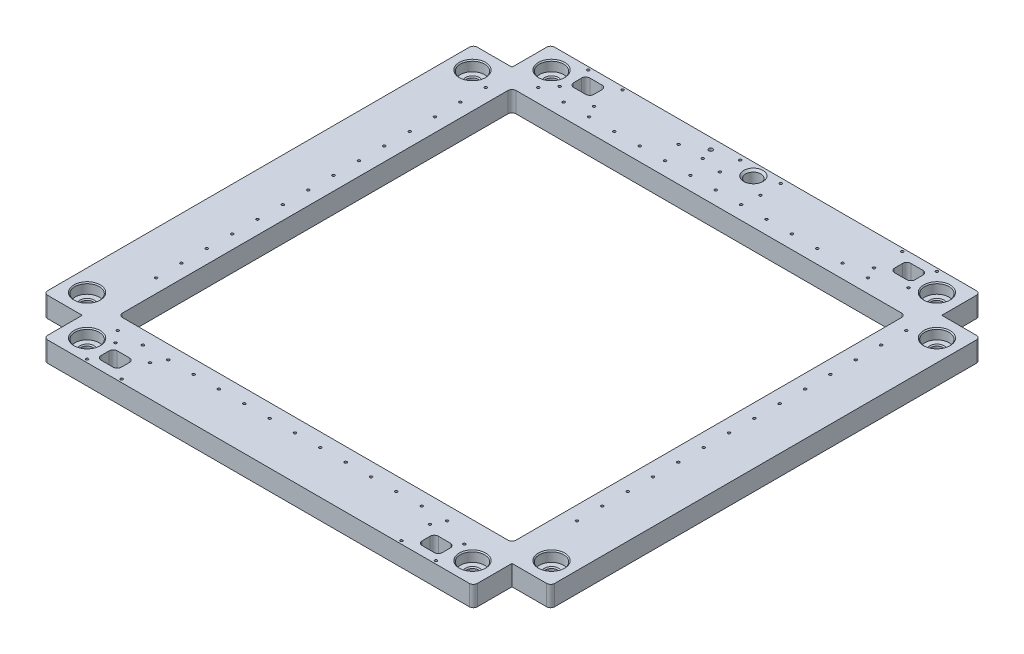
SolidWorks part; units mm, degrees
material "ASTM A36 Steel"
ref_plane "Front Plane" through (0, 0, 0) normal (0, 0, 1) x (1, 0, 0)
ref_plane "Top Plane" through (0, 0, 0) normal (0, 1, 0) x (1, 0, 0)
ref_plane "Right Plane" through (0, 0, 0) normal (1, 0, 0) x (0, 0, -1)
sketch "Sketch1" plane through (0, 0, 0) normal (0, 1, 0) x (1, 0, 0)
  line L1 (250, -250) -> (-250, -250)
  line L2 (250, -250) -> (250, 250)
  line L3 (250, 250) -> (-250, 250)
  line L4 (-250, -250) -> (-250, 250)
  line L5 (250, -250) -> (-250, 250) construction
  line L6 (250, 250) -> (-250, -250) construction
  point P0 (0, 0)
  dimension "D1" = 500
  dimension "D2" = 500
extrude "Boss-Extrude1" add sketch "Sketch1" along normal blind 20
sketch "Sketch2" plane through (0, 20, 0) normal (0, 1, 0) x (1, 0, 0)
  line L0 (250, 250) -> (-250, 250) construction
  line L10 (-250, 250) -> (-250, -250) construction
  line L15 (-250, 169) -> (-208, 169)
  line L16 (-250, 169) -> (-250, 211)
  line L17 (-174.5, 213.5) -> (-205.5, 213.5)
  line L27 (-250, 211) -> (-208, 211)
  line L33 (-208, 169) -> (-208, 211)
  line L35 (-250, 169) -> (-208, 211) construction
  line L36 (-250, 211) -> (-208, 169) construction
  line L37 (-169, 208) -> (-211, 208)
  line L38 (-169, 208) -> (-169, 250)
  line L39 (-169, 250) -> (-211, 250)
  line L40 (-211, 208) -> (-211, 250)
  line L41 (-169, 208) -> (-211, 250) construction
  line L42 (-169, 250) -> (-211, 208) construction
  line L43 (-208, 206) -> (-213, 211)
  line L44 (-174.5, 213.5) -> (-174.5, 244.5)
  line L45 (-174.5, 244.5) -> (-205.5, 244.5)
  line L46 (-205.5, 213.5) -> (-205.5, 244.5)
  line L47 (-174.5, 213.5) -> (-205.5, 244.5) construction
  line L48 (-174.5, 244.5) -> (-205.5, 213.5) construction
  line L49 (-213.5, 174.5) -> (-244.5, 174.5)
  line L50 (-213.5, 174.5) -> (-213.5, 205.5)
  line L51 (-213.5, 205.5) -> (-244.5, 205.5)
  line L52 (-244.5, 174.5) -> (-244.5, 205.5)
  line L53 (-213.5, 174.5) -> (-244.5, 205.5) construction
  line L54 (-213.5, 205.5) -> (-244.5, 174.5) construction
  line L55 (-206, 208) -> (-211, 213)
  line L56 (-213, 211) -> (-211, 213) construction
  point P1 (-229, 190)
  point P5 (-190, 229)
  point P23 (-229, 190)
  point P27 (-190, 229)
  dimension "D1" = 5
  dimension "D2" = 45
  dimension "D3" = 42
  dimension "D4" = 31
  dimension "D5" = 45
  dimension "D6" = 5
  dimension "D7" = 60
hole_wizard "Bearing Press Fit" positions "Sketch8" profile "Sketch9" hole size "Ø12.0" standard "ANSI Metric" end condition through all
sketch "Sketch8" plane through (0, 20, 0) normal (0, 1, 0) x (1, 0, 0)
  line L1 (-169, 250) -> (-211, 208) construction
  point P8 (-190, 229)
  point P12 (-229, 190)
sketch "Sketch9" plane through (-190, 20, -229) normal (1, 0, 0) x (0, 0, 1)
  line L0 (0, 0) -> (0, 20)
  line L1 (0, 20) -> (6, 20)
  line L2 (6, 20) -> (6, 0)
  line L5 (6, 0) -> (0, 0)
  line L11 (0, -6.35) -> (0, 107.95) construction
  dimension "Thru Hole Dia." = 12
  dimension "Thru Hole Depth" = 20
ref_axis "Axis1" through (0, 21, 0) along (0, -1, 0)
pattern_circular "CirPattern1" count 4 over 360 about axis through (0, 21, 0) along (0, -1, 0) of "Bearing Press Fit"
sketch "Sketch5" plane through (0, 20, 0) normal (0, 1, 0) x (1, 0, 0)
  line L1 (194, -194) -> (-194, -194)
  line L2 (194, -194) -> (194, 194)
  line L3 (194, 194) -> (-194, 194)
  line L4 (-194, -194) -> (-194, 194)
  line L5 (194, -194) -> (-194, 194) construction
  line L6 (194, 194) -> (-194, -194) construction
  point P0 (0, 0)
  dimension "D1" = 388
extrude "Cut-Extrude1" cut sketch "Sketch5" against normal up to surface (20 mm away) up to face at (-229, 0, 196)
sketch "Sketch10" plane through (0, 0, 0) normal (0, 1, 0) x (1, 0, 0)
  line L5 (194, 194) -> (-194, 194) construction
  line L6 (214, -214) -> (-214, -214)
  line L14 (214, -214) -> (214, 214)
  line L15 (214, 214) -> (-214, 214)
  line L16 (-214, -214) -> (-214, 214)
  line L17 (214, -214) -> (-214, 214) construction
  line L18 (214, 214) -> (-214, -214) construction
  line L19 (201.5, -201.5) -> (-201.5, -201.5)
  line L20 (201.5, -201.5) -> (201.5, 201.5)
  line L21 (201.5, 201.5) -> (-201.5, 201.5)
  line L22 (-201.5, -201.5) -> (-201.5, 201.5)
  line L23 (201.5, -201.5) -> (-201.5, 201.5) construction
  line L24 (201.5, 201.5) -> (-201.5, -201.5) construction
  point P0 (0, 0)
  point P6 (0, 0)
  dimension "D2" = 7.5
  dimension "D1" = 12.5
extrude "Linear Rail Slot" cut sketch "Sketch10" along normal blind 2.5
fillet "Fillet2" radius 4 4 edges at (-194, 10, 194) (194, 10, 194) (194, 10, -194) (-194, 10, -194)
sketch "Sketch11" plane through (0, 2.5, 0) normal (0, -1, 0) x (1, 0, 0)
  line L0 (-204, 207.5) -> (156, 207.5)
  line L1 (-201.5, 201.5) -> (201.5, 201.5) construction
  line L3 (-214, -214) -> (-214, 214) construction
  point P16 (143.5, 207.5)
  point P18 (118.5, 207.5)
  point P19 (93.5, 207.5)
  point P20 (68.5, 207.5)
  point P21 (43.5, 207.5)
  point P22 (18.5, 207.5)
  point P23 (-6.5, 207.5)
  point P24 (-31.5, 207.5)
  point P25 (-56.5, 207.5)
  point P26 (-81.5, 207.5)
  point P28 (-106.5, 207.5)
  point P29 (-131.5, 207.5)
  point P30 (-156.5, 207.5)
  point P31 (-181.5, 207.5)
  dimension "D1" = 360
  dimension "D2" = 6
  dimension "D4" = 14
  dimension "D5" = 25
  dimension "D6" = 10
  dimension "D3" = 12.5
hole_wizard "Tap Drill for M3x0.5 Tap1" positions "Sketch12" profile "Sketch13" hole size "M3x0.5" standard "ANSI Metric" end condition through all
sketch "Sketch12" plane through (0, 2.5, 0) normal (0, -1, 0) x (-1, 0, 0)
  line L0 (204, -207.5) -> (-156, -207.5) construction
  point P28 (-143.5, -207.5)
  point P31 (-118.5, -207.5)
  point P34 (-93.5, -207.5)
  point P37 (-68.5, -207.5)
  point P40 (-43.5, -207.5)
  point P43 (-18.5, -207.5)
  point P46 (6.5, -207.5)
  point P49 (31.5, -207.5)
  point P51 (56.5, -207.5)
  point P54 (81.5, -207.5)
  point P57 (106.5, -207.5)
  point P61 (131.5, -207.5)
  point P64 (156.5, -207.5)
  point P67 (181.5, -207.5)
sketch "Sketch13" plane through (143.5, 2.5, 207.5) normal (1, 0, 0) x (0, 0, -1)
  line L0 (0, 0) -> (0, 17.5)
  line L1 (0, 17.5) -> (1.25, 17.5)
  line L2 (1.25, 17.5) -> (1.25, 0)
  line L5 (1.25, 0) -> (0, 0)
  line L11 (0, -6.35) -> (0, 107.95) construction
  dimension "Thru Hole Dia." = 2.5
  dimension "Thru Hole Depth" = 17.5
sketch "Sketch14" plane through (0, 0, 0) normal (0, -1, 0) x (1, 0, 0)
  line L1 (-156.5, 213.5) -> (-181.5, 213.5)
  line L2 (-152.5, 217.5) -> (-152.5, 219.5)
  line L3 (-156.5, 223.5) -> (-181.5, 223.5)
  line L4 (-185.5, 217.5) -> (-185.5, 219.5)
  line L5 (-152.5, 213.5) -> (-185.5, 223.5) construction
  line L6 (-152.5, 223.5) -> (-185.5, 213.5) construction
  line L7 (-201.5, 201.5) -> (201.5, 201.5) construction
  line L8 (-181.5, 207.5) -> (-156.5, 207.5) construction
  line L19 (-6.5, 213.5) -> (-31.5, 213.5)
  line L25 (-2.5, 217.5) -> (-2.5, 219.5)
  line L26 (-6.5, 223.5) -> (-31.5, 223.5)
  line L31 (-35.5, 217.5) -> (-35.5, 219.5)
  line L32 (-2.5, 213.5) -> (-35.5, 223.5) construction
  line L33 (-2.5, 223.5) -> (-35.5, 213.5) construction
  line L34 (-31.5, 207.5) -> (-6.5, 207.5) construction
  line L35 (143.5, 213.5) -> (118.5, 213.5)
  line L36 (147.5, 217.5) -> (147.5, 219.5)
  line L37 (143.5, 223.5) -> (118.5, 223.5)
  line L38 (114.5, 217.5) -> (114.5, 219.5)
  line L39 (147.5, 213.5) -> (114.5, 223.5) construction
  line L40 (147.5, 223.5) -> (114.5, 213.5) construction
  line L41 (118.5, 207.5) -> (143.5, 207.5) construction
  arc A3 (-152.5, 219.5) -> (-156.5, 223.5) centre (-156.5, 219.5) ccw
  arc A4 (-156.5, 213.5) -> (-152.5, 217.5) centre (-156.5, 217.5) ccw
  arc A5 (-181.5, 213.5) -> (-185.5, 217.5) centre (-181.5, 217.5) cw
  arc A6 (-181.5, 223.5) -> (-185.5, 219.5) centre (-181.5, 219.5) ccw
  arc A7 (-2.5, 219.5) -> (-6.5, 223.5) centre (-6.5, 219.5) ccw
  arc A8 (-6.5, 213.5) -> (-2.5, 217.5) centre (-6.5, 217.5) ccw
  arc A9 (-31.5, 213.5) -> (-35.5, 217.5) centre (-31.5, 217.5) cw
  arc A10 (-31.5, 223.5) -> (-35.5, 219.5) centre (-31.5, 219.5) ccw
  arc A11 (147.5, 219.5) -> (143.5, 223.5) centre (143.5, 219.5) ccw
  arc A12 (143.5, 213.5) -> (147.5, 217.5) centre (143.5, 217.5) ccw
  arc A13 (118.5, 213.5) -> (114.5, 217.5) centre (118.5, 217.5) cw
  arc A14 (118.5, 223.5) -> (114.5, 219.5) centre (118.5, 219.5) ccw
  point P0 (-169, 218.5)
  point P12 (-169, 207.5)
  point P26 (-19, 218.5)
  point P45 (131, 218.5)
  dimension "D5" = 3
  dimension "D4" = 4
  dimension "D1" = 33
  dimension "D2" = 12
  dimension "D3" = 10
  dimension "D7" = 25
  dimension "D6" = 150
mirror "Mirror5" about plane through (0, 0, 0) normal (0, 0, 1) of "Tap Drill for M3x0.5 Tap1"
ref_plane "Plane1" through (0, 0, 0) normal (-0.7071, 0, 0.7071) x (0.7071, 0, 0.7071)
mirror "Mirror6" about plane through (0, 0, 0) normal (-0.7071, 0, 0.7071) of "Mirror5"
sketch "Sketch19" plane through (0, 2.5, 0) normal (0, -1, 0) x (1, 0, 0)
  line L0 (-198.5, 201.5) -> (-198.5, 214)
  line L1 (-201.5, 201.5) -> (201.5, 201.5) construction
  line L2 (-214, 214) -> (214, 214) construction
  line L3 (-198.5, 214) -> (-214, 214)
  line L4 (-214, 214) -> (-214, 198.5)
  line L5 (-214, -214) -> (-214, 214) construction
  line L6 (-214, 198.5) -> (-201.5, 198.5)
  line L7 (-201.5, -201.5) -> (-201.5, 201.5) construction
  line L8 (-201.5, 198.5) -> (-201.5, 201.5)
  line L9 (-201.5, 201.5) -> (-198.5, 201.5)
  dimension "D1" = 3
extrude "Boss-Extrude2" add sketch "Sketch19" along normal up to surface (2.5 mm away) up to face at (-229, 0, 196)
pattern_circular "CirPattern4" count 4 over 360 about axis through (0, 21, 0) along (0, -1, 0) of "Boss-Extrude2"
sketch "Sketch20" plane through (0, 20, 0) normal (0, 1, 0) x (1, 0, 0)
  line L5 (-250, -250) -> (250, -250) construction
  line L20 (148.3, -225) -> (168.3, -241) construction
  line L23 (168.3, -225) -> (148.3, -241) construction
  line L28 (122, -247) -> (172, -219) construction
  line L29 (172, -247) -> (122, -219) construction
  line L30 (172, -219) -> (122, -219) construction
  line L31 (122, -247) -> (122, -219) construction
  line L32 (172, -247) -> (122, -247) construction
  line L33 (172, -247) -> (172, -219) construction
  line L34 (164.3, -241) -> (152.3, -241)
  line L35 (148.3, -229) -> (148.3, -237)
  line L36 (164.3, -225) -> (152.3, -225)
  line L37 (168.3, -229) -> (168.3, -237)
  arc A12 (152.3, -225) -> (148.3, -229) centre (152.3, -229) ccw
  arc A13 (148.3, -237) -> (152.3, -241) centre (152.3, -237) ccw
  arc A14 (168.3, -237) -> (164.3, -241) centre (164.3, -237) cw
  arc A15 (168.3, -229) -> (164.3, -225) centre (164.3, -229) ccw
  circle A16 centre (190, -229) radius 6 construction
  point P8 (0, 0)
  point P65 (158.3, -233)
  point P66 (147, -233)
  point P67 (158.3, -233)
  dimension "D7" = 31.7
  dimension "D8" = 11.3
  dimension "D6" = 4
  dimension "D1" = 28
  dimension "D2" = 50
  dimension "D3" = 17
  dimension "D4" = 20
  dimension "D5" = 16
extrude "Cut-Extrude3" cut sketch "Sketch20" against normal through all
hole_wizard "Tap Drill for M3x0.5 Tap6" positions "Sketch39" profile "Sketch40" hole size "M3x0.5" standard "ANSI Metric"
sketch "Sketch39" plane through (0, 20, 0) normal (0, 1, 0) x (1, 0, 0)
  line L1 (172, -247) -> (138, -247)
  line L2 (172, -247) -> (172, -219)
  line L3 (172, -219) -> (138, -219)
  line L4 (138, -247) -> (138, -219)
  line L5 (-250, -250) -> (250, -250) construction
  circle A0 centre (190, -229) radius 6 construction
  point P1 (172, -247)
  point P2 (138, -219)
  point P99 (172, -219)
  point P100 (138, -247)
  dimension "D1" = 34
  dimension "D2" = 28
  dimension "D3" = 3
  dimension "D4" = 18
sketch "Sketch40" plane through (172, 20, 247) normal (1, 0, 0) x (0, 0, 1)
  line L0 (0, 0) -> (0, 20)
  line L1 (0, 20) -> (1.25, 20)
  line L2 (1.25, 20) -> (1.25, 0)
  line L5 (1.25, 0) -> (0, 0)
  line L10 (0, 20) -> (-1.25, 20) construction
  line L11 (0, -6.35) -> (0, 107.95) construction
  dimension "Hole Dia." = 2.5
  dimension "Hole Depth" = 20
  dimension "Drill Angle" = 180
mirror "Mirror8" about plane through (0, 0, 0) normal (1, 0, 0) of "Tap Drill for M3x0.5 Tap6", "Cut-Extrude3"
mirror "Mirror9" about plane through (0, 0, 0) normal (0, 0, 1) of "Mirror8"
sketch "Sketch27" plane through (0, 20, 0) normal (0, 1, 0) x (1, 0, 0)
  line L1 (250, -250) -> (211.9, -250)
  line L2 (250, -250) -> (250, -211.9)
  line L3 (250, -211.9) -> (211.9, -211.9)
  line L4 (211.9, -250) -> (211.9, -211.9)
  dimension "D1" = 38.1
extrude "Cut-Extrude4" cut sketch "Sketch27" against normal up to surface (20 mm away) up to face at (172, 0, -245.75)
pattern_circular "CirPattern3" count 4 over 360 about axis through (0, 21, 0) along (0, -1, 0) of "Cut-Extrude4"
fillet "Fillet5" radius 4 16 edges at (198.5, 1.25, 214) (198.5, 1.25, 201.5) (201.5, 1.25, 198.5) (214, 1.25, 198.5) (-214, 1.25, 198.5) (-198.5, 1.25, 214) (-201.5, 1.25, 198.5) (-198.5, 1.25, 201.5) (-214, 1.25, -198.5) (-198.5, 1.25, -214) (-198.5, 1.25, -201.5) (-201.5, 1.25, -198.5) (198.5, 1.25, -201.5) (198.5, 1.25, -214) (201.5, 1.25, -198.5) (214, 1.25, -198.5)
hole_wizard "Tap Drill for M3x0.5 Tap4" positions "Sketch35" profile "Sketch36" hole size "M3x0.5" standard "ANSI Metric" end condition up to next
sketch "Sketch35" plane through (0, 20, 0) normal (0, 1, 0) x (1, 0, 0)
  line L1 (20, 225) -> (-20, 225)
  line L2 (20, 225) -> (20, 245)
  line L3 (20, 245) -> (-20, 245)
  line L4 (-20, 225) -> (-20, 245)
  line L5 (20, 225) -> (-20, 245) construction
  line L6 (20, 245) -> (-20, 225) construction
  line L7 (211.9, 250) -> (-211.9, 250) construction
  point P2 (-20, 245)
  point P53 (20, 225)
  point P54 (20, 245)
  point P55 (-20, 225)
  point P69 (0, 235)
  dimension "D1" = 20
  dimension "D2" = 40
  dimension "D3" = 15
sketch "Sketch36" plane through (-20, 20, -245) normal (1, 0, 0) x (0, 0, 1)
  line L0 (0, 0) -> (0, 20)
  line L1 (0, 20) -> (1.25, 20)
  line L2 (1.25, 20) -> (1.25, 0)
  line L5 (1.25, 0) -> (0, 0)
  line L11 (0, -6.35) -> (0, 107.95) construction
  dimension "Thru Hole Dia." = 2.5
  dimension "Thru Hole Depth" = 20
hole_wizard "Ø15.0 (15) Diameter Hole2" positions "Sketch37" profile "Sketch38" hole size "Ø15.0" standard "ANSI Metric" end condition up to next
sketch "Sketch37" plane through (0, 20, 0) normal (0, 1, 0) x (1, 0, 0)
  circle A0 centre (0, 235) radius 1.25 construction
  point P0 (0, 238)
  dimension "D1" = 3
sketch "Sketch38" plane through (0, 20, -238) normal (1, 0, 0) x (0, 0, 1)
  line L0 (0, 0) -> (0, 20)
  line L1 (0, 20) -> (7.5, 20)
  line L2 (7.5, 20) -> (7.5, 0)
  line L5 (7.5, 0) -> (0, 0)
  line L11 (0, -6.35) -> (0, 107.95) construction
  dimension "Thru Hole Dia." = 15
  dimension "Thru Hole Depth" = 20
chamfer "Chamfer1" distance 2 angle 45 2 edges at (0, 0, -230.5) (0, 20, -230.5)
hole_wizard "Ø24.0 (24) Diameter Hole1" positions "Sketch41" profile "Sketch42" hole size "Ø24.0" standard "ANSI Metric"
sketch "Sketch41" plane through (0, 20, 0) normal (0, 1, 0) x (1, 0, 0)
  point P0 (-229, -190)
  point P3 (-190, -229)
  point P6 (190, -229)
  point P9 (229, -190)
  point P12 (229, 190)
  point P15 (190, 229)
  point P18 (-190, 229)
  point P21 (-229, 190)
sketch "Sketch42" plane through (-229, 20, 190) normal (1, 0, 0) x (0, 0, 1)
  line L0 (0, 0) -> (0, 10)
  line L1 (0, 10) -> (12, 10)
  line L2 (12, 10) -> (12, 0)
  line L5 (12, 0) -> (0, 0)
  line L10 (0, 10) -> (-12, 10) construction
  line L11 (0, -6.35) -> (0, 107.95) construction
  dimension "Hole Dia." = 24
  dimension "Hole Depth" = 10
  dimension "Drill Angle" = 180
chamfer "Chamfer2" distance 1 angle 45 24 edges at (-229, 0, -184) (-229, 10, -196) (-190, 0, -223) (-190, 10, -235) (229, 0, -184) (229, 10, -196) (190, 0, -223) (190, 10, -235) (229, 0, 196) (229, 10, 184) (190, 0, 235) (190, 10, 223) (-190, 0, 235) (-190, 10, 223) (-229, 0, 196) (-229, 10, 184) (-229, 20, -178) (-190, 20, -217) (229, 20, -178) (190, 20, -217) (229, 20, 202) (190, 20, 241) (-190, 20, 241) (-229, 20, 202)
fillet "Fillet6" radius 4 8 edges at (250, 10, -211.9) (211.9, 10, -250) (-211.9, 10, -250) (-250, 10, -211.9) (211.9, 10, 250) (250, 10, 211.9) (-211.9, 10, 250) (-250, 10, 211.9)
hole_wizard "Tap Drill for M3x0.5 Tap7" positions "Sketch43" profile "Sketch44" hole size "M3x0.5" standard "ANSI Metric" end condition up to next
sketch "Sketch43" plane through (0, 20, 0) normal (0, 1, 0) x (1, 0, 0)
  line L0 (-63.7737, 228) -> (-39.7737, 228) construction
  line L2 (207.9, 250) -> (-207.9, 250) construction
  circle A0 centre (-20, 225) radius 1.25 construction
  point P1 (-63.7737, 228)
  point P2 (-39.7737, 228)
  dimension "D3" = 20
  dimension "D1" = 22
  dimension "D2" = 24
sketch "Sketch44" plane through (-63.7737, 20, -228) normal (1, 0, 0) x (0, 0, 1)
  line L0 (0, 0) -> (0, 20)
  line L1 (0, 20) -> (1.25, 20)
  line L2 (1.25, 20) -> (1.25, 0)
  line L5 (1.25, 0) -> (0, 0)
  line L11 (0, -6.35) -> (0, 107.95) construction
  dimension "Thru Hole Dia." = 2.5
  dimension "Thru Hole Depth" = 20
hole_wizard "Ø4.0 (4) Diameter Hole1" positions "Sketch45" profile "Sketch46" hole size "Ø4.0" standard "ANSI Metric" end condition up to next
sketch "Sketch45" plane through (0, 20, 0) normal (0, 1, 0) x (1, 0, 0)
  circle A0 centre (-63.7737, 228) radius 1.25 construction
  point P0 (-43.4737, 239.5)
  dimension "D1" = 20.3
  dimension "D2" = 11.5
sketch "Sketch46" plane through (-43.4737, 20, -239.5) normal (1, 0, 0) x (0, 0, 1)
  line L0 (0, 0) -> (0, 20)
  line L1 (0, 20) -> (2, 20)
  line L2 (2, 20) -> (2, 0)
  line L5 (2, 0) -> (0, 0)
  line L11 (0, -6.35) -> (0, 107.95) construction
  dimension "Thru Hole Dia." = 4
  dimension "Thru Hole Depth" = 20
